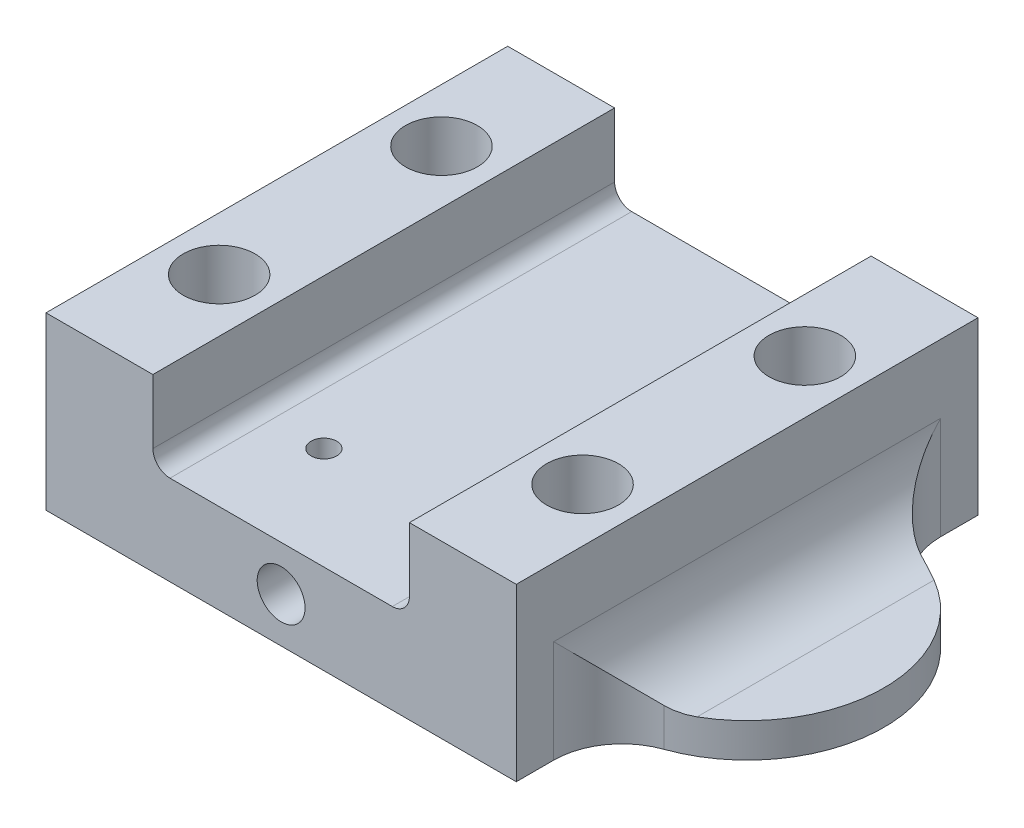
SolidWorks part; units mm, degrees
ref_plane "Front Plane" through (0, 0, 0) normal (0, 0, 1) x (1, 0, 0)
ref_plane "Top Plane" through (0, 0, 0) normal (0, 1, 0) x (1, 0, 0)
ref_plane "Right Plane" through (0, 0, 0) normal (1, 0, 0) x (0, 0, -1)
sketch "Sketch1" plane through (0, 0, 0) normal (0, 0, 1) x (1, 0, 0)
  line L0 (0, 4.75) -> (0, -4.75) construction
  line L1 (-7.5, -4.75) -> (7.5, -4.75)
  line L2 (-7.5, -4.75) -> (-7.5, 4.75)
  line L3 (-7.5, 4.75) -> (7.5, 4.75)
  line L4 (7.5, -4.75) -> (7.5, 4.75)
  line L5 (-7.5, -4.75) -> (7.5, 4.75) construction
  line L6 (-7.5, 4.75) -> (7.5, -4.75) construction
  line L7 (-3.5, -3.75) -> (-3.5, -4.75) construction
  line L8 (-13.75, 0) -> (13.75, 0)
  line L9 (-13.75, -10) -> (13.75, -10)
  line L10 (-13.75, -10) -> (-13.75, 10)
  line L11 (-13.75, 10) -> (13.75, 10)
  line L12 (13.75, -10) -> (13.75, 10)
  line L13 (-13.75, -10) -> (13.75, 10) construction
  line L14 (-13.75, 10) -> (13.75, -10) construction
  circle A0 centre (-3.5, -0.75) radius 3
  circle A1 centre (3.5, -0.75) radius 3
  point P0 (0, 0)
  point P14 (0, 0)
  point P22 (-13.75, 0)
  dimension "D4" = 6
  dimension "D1" = 9.5
  dimension "D2" = 15
  dimension "D3" = 4
  dimension "D5" = 4
  dimension "D6" = 20
  dimension "D7" = 27.5
extrude "Boss-Extrude1" add sketch "Sketch1" along normal blind 27 contours L9 L12 L8 L4 L1 L2 L10 region at (0, -5.9179, 0)
sketch "Sketch2" plane through (0, -10, 0) normal (0, -1, 0) x (1, 0, 0)
  line L0 (13.75, 27) -> (13.75, 0) construction
  line L1 (13.75, 21.5) -> (13.75, 5.5)
  line L2 (0, 0) -> (0, 27) construction
  line L3 (-7.5, 27) -> (7.5, 27) construction
  line L4 (-13.75, 27) -> (-13.75, 0) construction
  line L5 (-13.75, 21.5) -> (-13.75, 5.5)
  arc A0 (13.75, 5.5) -> (13.75, 21.5) centre (13.75, 13.5) ccw
  arc A1 (-13.75, 5.5) -> (-13.75, 21.5) centre (-13.75, 13.5) cw
  dimension "D1" = 8
extrude "Boss-Extrude2" add sketch "Sketch2" against normal blind 2
sketch "Sketch3" plane through (0, 0, 0) normal (0, 1, 0) x (1, 0, 0)
  line L0 (-7.5, -27) -> (-7.5, 0) construction
  line L1 (-7.5, -27) -> (-7.5, 0)
  line L2 (-13.75, -27) -> (-13.75, 0) construction
  line L3 (-13.75, -27) -> (-13.75, 0)
  line L4 (-13.75, -27) -> (-7.5, -27) construction
  line L5 (-10.625, 0) -> (-10.625, -27) construction
  line L8 (0, 0) -> (0, -27) construction
  line L9 (-7.5, -27) -> (7.5, -27) construction
  line L10 (-13.75, 0) -> (-7.5, 0) construction
  line L11 (-13.75, -13.5) -> (13.75, -13.5) construction
  line L12 (13.75, -21.5) -> (13.75, -5.5) construction
  circle A0 centre (-10.625, -20) radius 2.1
  circle A1 centre (10.625, -20) radius 2.1
  circle A2 centre (10.625, -7) radius 2.1
  circle A3 centre (-10.625, -7) radius 2.1
  dimension "D1" = 4.2
  dimension "D2" = 7
extrude "Cut-Extrude1" cut sketch "Sketch3" against normal through all contours A0 | A1 | A3 | A2 region at (-10.625, 0, 20) region at (10.625, 0, 20) region at (10.625, 0, 7) region at (-10.625, 0, 7)
sketch "Sketch4" plane through (0, 0, 27) normal (0, 0, 1) x (1, 0, 0)
  line L0 (0, -4.75) -> (0, -10) construction
  line L8 (-13.75, -10) -> (13.75, -10)
  line L9 (13.75, -10) -> (13.75, 0)
  line L10 (13.75, 0) -> (7.5, 0)
  line L11 (7.5, 0) -> (7.5, -4.75)
  line L12 (7.5, -4.75) -> (-7.5, -4.75)
  line L13 (-7.5, -4.75) -> (-7.5, 0)
  line L15 (-13.75, 0) -> (-13.75, -10)
  line L16 (-13.75, -10) -> (13.75, -10)
  line L17 (13.75, -10) -> (13.75, 0)
  line L19 (7.5, 0) -> (7.5, -4.75)
  line L20 (7.5, -4.75) -> (-7.5, -4.75)
  line L21 (-7.5, -4.75) -> (-7.5, 0)
  line L23 (-13.75, 0) -> (-13.75, -10)
  line L25 (13.75, 0) -> (7.5, 0)
  line L27 (-7.5, 0) -> (-13.75, 0)
  line L28 (-7.5, 0) -> (-13.75, 0)
  circle A2 centre (0, -7.375) radius 1.4
  dimension "D4" = 2.8
  dimension "D1" = 0
extrude "Cut-Extrude2" cut sketch "Sketch4" against normal through all contours L0 A2 | A2 L0 region at (0.5942, -7.375, 27) region at (-0.5942, -7.375, 27)
fillet "Fillet1" radius 1 2 edges at (7.5, -4.75, 13.5) (-7.5, -4.75, 13.5)
fillet "Fillet2" radius 4 6 edges at (13.75, -9, 5.5) (13.75, -8, 13.5) (13.75, -9, 21.5) (-13.75, -9, 5.5) (-13.75, -8, 13.5) (-13.75, -9, 21.5)
sketch "Sketch5" plane through (0, -4.75, 0) normal (0, 1, 0) x (1, 0, 0)
  line L0 (6.5, -27) -> (6.5, 0) construction
  line L1 (-6.5, -27) -> (6.5, -27) construction
  line L2 (-6.5, 0) -> (6.5, 0) construction
  line L3 (-6.5, 0) -> (-6.5, -27) construction
  circle A0 centre (3.5, -6) radius 0.75
  circle A1 centre (-3.5, -21) radius 0.75
  dimension "D1" = 1.5
  dimension "D2" = 1.5
  dimension "D3" = 6
  dimension "D4" = 6
  dimension "D5" = 3
  dimension "D6" = 3
extrude "Cut-Extrude3" cut sketch "Sketch5" against normal through all contours A1 | A0 | A0 | A1 region at (3.5, -4.75, 6) region at (-3.5, -4.75, 21)
